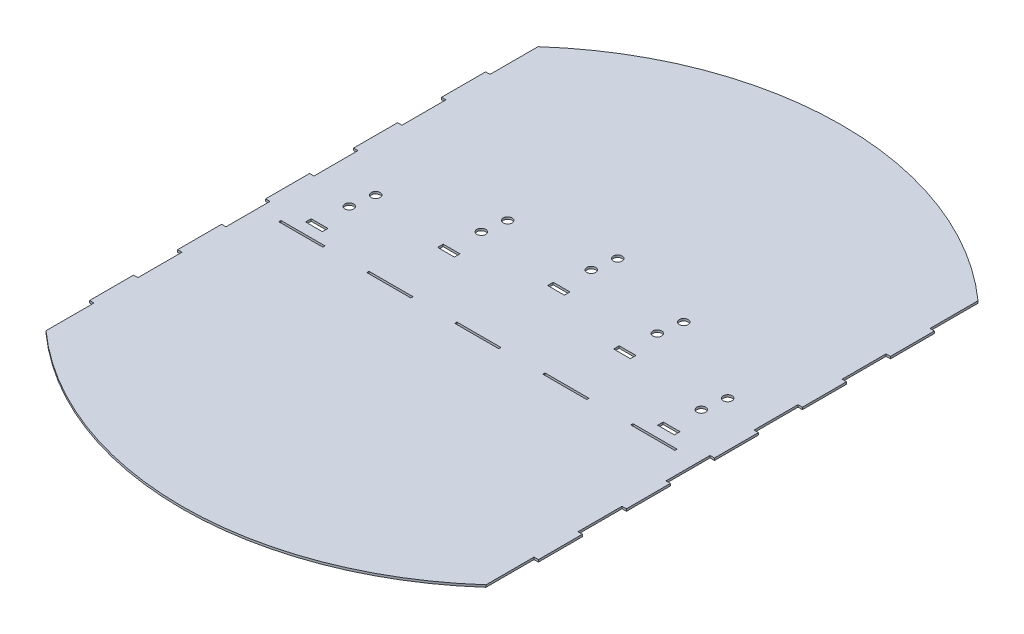
SolidWorks part; units mm, degrees
ref_plane "Přední rovina" through (0, 0, 0) normal (0, 0, 1) x (1, 0, 0)
ref_plane "Horní rovina" through (0, 0, 0) normal (0, 1, 0) x (1, 0, 0)
ref_plane "Pravá rovina" through (0, 0, 0) normal (1, 0, 0) x (0, 0, -1)
sketch "Skica1" plane through (0, 0, 0) normal (0, 1, 0) x (1, 0, 0)
  line L0 (-150, 0) -> (150, 0)
  line L5 (-200, 111.8034) -> (-100, 111.8034)
  line L6 (-200, 111.8034) -> (-200, -111.8034)
  line L7 (-200, -111.8034) -> (-100, -111.8034)
  line L8 (-100, 111.8034) -> (-100, -111.8034)
  line L9 (-200, 111.8034) -> (-100, -111.8034) construction
  line L10 (-200, -111.8034) -> (-100, 111.8034) construction
  line L15 (200, -111.8034) -> (100, -111.8034)
  line L16 (100, 111.8034) -> (100, -111.8034)
  line L17 (-100, -90) -> (-102, -90)
  line L18 (-100, -90) -> (-100, -70)
  line L19 (-100, -70) -> (-102, -70)
  line L20 (-102, -90) -> (-102, -70)
  line L21 (-100, -50) -> (-102, -50)
  line L22 (-100, -50) -> (-100, -30)
  line L23 (-100, -30) -> (-102, -30)
  line L24 (-102, -50) -> (-102, -30)
  line L25 (0, -150) -> (0, 150)
  line L26 (-100, 30) -> (-102, 30)
  line L27 (-102, 50) -> (-102, 30)
  line L28 (-100, 50) -> (-102, 50)
  line L29 (-100, 50) -> (-100, 30)
  line L30 (-100, 70) -> (-102, 70)
  line L31 (-102, 90) -> (-102, 70)
  line L32 (-100, 90) -> (-102, 90)
  line L33 (-100, 90) -> (-100, 70)
  line L34 (200, 111.8034) -> (100, 111.8034)
  line L35 (200, 111.8034) -> (200, -111.8034)
  line L36 (100, 90) -> (100, 70)
  line L37 (100, 90) -> (102, 90)
  line L38 (102, 90) -> (102, 70)
  line L39 (100, 70) -> (102, 70)
  line L40 (100, 50) -> (100, 30)
  line L41 (100, 50) -> (102, 50)
  line L42 (102, 50) -> (102, 30)
  line L43 (100, 30) -> (102, 30)
  line L44 (100, -30) -> (102, -30)
  line L45 (102, -50) -> (102, -30)
  line L46 (100, -50) -> (102, -50)
  line L47 (100, -50) -> (100, -30)
  line L48 (100, -70) -> (102, -70)
  line L49 (102, -90) -> (102, -70)
  line L50 (100, -90) -> (102, -90)
  line L51 (100, -90) -> (100, -70)
  line L52 (-3.81, 22.54) -> (3.81, 22.54)
  line L53 (-83.81, -10) -> (-76.19, -10)
  line L54 (-83.81, -10) -> (-83.81, -7.46)
  line L55 (-83.81, -7.46) -> (-76.19, -7.46)
  line L56 (-76.19, -10) -> (-76.19, -7.46)
  line L57 (-3.81, 22.54) -> (-3.81, 20)
  line L58 (-3.81, 20) -> (3.81, 20)
  line L59 (3.81, 22.54) -> (3.81, 20)
  line L60 (-43.81, 10) -> (-36.19, 10)
  line L61 (-43.81, 10) -> (-43.81, 12.54)
  line L62 (-43.81, 12.54) -> (-36.19, 12.54)
  line L63 (-36.19, 10) -> (-36.19, 12.54)
  line L64 (43.81, 10) -> (43.81, 12.54)
  line L65 (43.81, 12.54) -> (36.19, 12.54)
  line L66 (36.19, 10) -> (36.19, 12.54)
  line L67 (43.81, 10) -> (36.19, 10)
  line L68 (83.81, -7.46) -> (76.19, -7.46)
  line L69 (76.19, -10) -> (76.19, -7.46)
  line L70 (83.81, -10) -> (76.19, -10)
  line L71 (83.81, -10) -> (83.81, -7.46)
  line L72 (100, 10) -> (102, 10)
  line L73 (-100, -10) -> (-102, -10)
  line L74 (-100, -10) -> (-100, 10)
  line L75 (-100, 10) -> (-102, 10)
  line L76 (-102, -10) -> (-102, 10)
  line L77 (102, -10) -> (102, 10)
  line L78 (100, -10) -> (102, -10)
  line L79 (100, -10) -> (100, 10)
  line L80 (-40, 12.54) -> (-40, 26.04)
  line L81 (-80, -7.46) -> (-80, 6.04)
  line L82 (40, 12.54) -> (40, 26.04)
  line L83 (80, -7.46) -> (80, 6.04)
  line L84 (-100, -15) -> (100, -15)
  line L85 (50, -16) -> (30, -16)
  line L86 (-90, -15) -> (-70, -15)
  line L87 (-90, -15) -> (-90, -16)
  line L88 (-90, -16) -> (-70, -16)
  line L89 (-70, -15) -> (-70, -16)
  line L90 (-50, -15) -> (-30, -15)
  line L91 (-50, -15) -> (-50, -16)
  line L92 (-50, -16) -> (-30, -16)
  line L93 (-30, -15) -> (-30, -16)
  line L94 (-10, -15) -> (10, -15)
  line L95 (-10, -15) -> (-10, -16)
  line L96 (-10, -16) -> (10, -16)
  line L97 (10, -15) -> (10, -16)
  line L98 (30, -15) -> (30, -16)
  line L99 (50, -15) -> (30, -15)
  line L100 (50, -15) -> (50, -16)
  line L101 (90, -16) -> (70, -16)
  line L102 (70, -15) -> (70, -16)
  line L103 (90, -15) -> (70, -15)
  line L104 (90, -15) -> (90, -16)
  circle A0 centre (0, 0) radius 150
  circle A1 centre (0, 36.04) radius 2
  circle A2 centre (1.5, 46.54) radius 2
  circle A3 centre (80, 6.04) radius 2
  circle A4 centre (40, 26.04) radius 2
  circle A5 centre (41.5, 36.54) radius 2
  circle A6 centre (81.5, 16.54) radius 2
  circle A7 centre (-40, 26.04) radius 2
  circle A8 centre (-38.5, 36.54) radius 2
  circle A9 centre (-80, 6.04) radius 2
  circle A10 centre (-78.5, 16.54) radius 2
  point P2 (-150, 0)
  point P8 (150, 0)
  point P17 (-101, -90)
  point P50 (-76.19, -8.73)
  point P64 (-80, -7.46)
  point P71 (-40, 12.54)
  dimension "D1" = 300
  dimension "D26" = 4
  dimension "D28" = 4
  dimension "D31" = 4
  dimension "D32" = 4
  dimension "D35" = 4
  dimension "D36" = 4
  dimension "D37" = 4
  dimension "D38" = 4
  dimension "D39" = 4
  dimension "D40" = 4
  dimension "D3" = 2
  dimension "D4" = 20
  dimension "D5" = 20
  dimension "D6" = 2
  dimension "D7" = 20
  dimension "D8" = 30
  dimension "D9" = 2.54
  dimension "D10" = 7.62
  dimension "D11" = 7.62
  dimension "D12" = 2.54
  dimension "D13" = 3.81
  dimension "D14" = 80
  dimension "D15" = 7.62
  dimension "D16" = 2.54
  dimension "D17" = 40
  dimension "D18" = 20
  dimension "D19" = 10
  dimension "D20" = 10
  dimension "D21" = 10
  dimension "D22" = 20
  dimension "D23" = 2
  dimension "D24" = 50
  dimension "D25" = 90
  dimension "D27" = 13.5
  dimension "D29" = 24
  dimension "D30" = 1.5
  dimension "D33" = 13.5
  dimension "D34" = 13.5
  dimension "D41" = 1.5
  dimension "D42" = 24
  dimension "D43" = 1.5
  dimension "D44" = 24
  dimension "D45" = 13.5
  dimension "D46" = 13.5
  dimension "D47" = 1.5
  dimension "D48" = 24
  dimension "D49" = 24
  dimension "D50" = 1.5
  dimension "D51" = 200
  dimension "D52" = 15
  dimension "D53" = 20
  dimension "D54" = 20
  dimension "D55" = 20
  dimension "D56" = 10
  dimension "D57" = 20
  dimension "D58" = 20
  dimension "D59" = 1
extrude "Přidat vysunutím1" add sketch "Skica1" along normal blind 1 contours L8 A0 L25 L96 L95 L84 L93 L92 L91 L89 L88 L87 | L25 A0 L16 L84 L104 L101 L102 L100 L85 L98 L97 L96 | A3 L0 L16 A0 L25 A2 A1 L52 L59 L58 A6 A5 A4 L65 L64 L67 L66 | A9 L0 L25 L58 L57 L52 A1 A2 A0 L8 A10 A8 A7 L62 L63 L60 L61 | L25 L84 L16 L0 L68 L71 L70 L69 | L8 L84 L25 L0 L55 L56 L53 L54 | L8 L32 L31 L30 | L76 L73 L8 L0 | L76 L0 L8 L75 | L20 L17 L8 L19 | L27 L26 L29 L28 | L24 L23 L22 L21 | L38 L39 L36 L37 | L42 L43 L40 L41 | L77 L72 L79 L78 | L45 L44 L47 L46 | L49 L48 L51 L50 region at (-101, 0, -5) region at (-101, 0, 5) region at (-47.7919, 0, -69.7559) region at (-47.4874, 0, 77.2521) region at (-49.6078, 0, 7.4839) region at (-101, 0, -80) region at (47.8225, 0, -69.7741) region at (-101, 0, 80) region at (47.4874, 0, 77.2521) region at (49.6078, 0, 7.4839)
